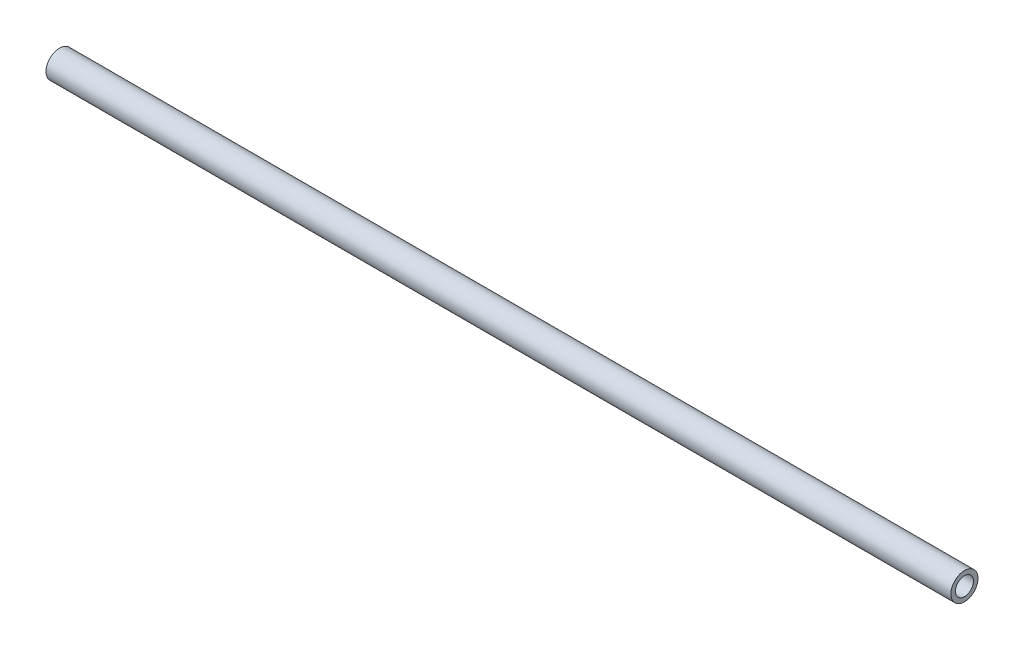
SolidWorks part; units mm, degrees
ref_plane "Front" through (0, 0, 0) normal (0, 0, 1) x (1, 0, 0)
ref_plane "Top" through (0, 0, 0) normal (0, 1, 0) x (1, 0, 0)
ref_plane "Right" through (0, 0, 0) normal (1, 0, 0) x (0, 0, -1)
sketch "Sketch1" plane through (0, 0, 0) normal (1, 0, 0) x (0, 0, -1)
  line L0 (6.35, 0) -> (9.525, 0) construction
  line L1 (6.35, 0) -> (9.525, 0) construction
  line L2 (7.9375, 0) -> (7.9375, 1.0672) construction
  circle A0 centre (0, 0) radius 9.525
  circle A1 centre (0, 0) radius 6.35
  point P4 (9.525, 0)
  point P5 (6.35, 0)
  dimension "OD" = 19.05
  dimension "ID" = 12.7
  dimension "Wall Thickness" = 3.175
sketch "Sketch2" plane through (0, 0, 0) normal (0, 0, 1) x (1, 0, 0)
  line L0 (-317.5, 0) -> (317.5, 0) construction
  point P2 (-293.6875, 0)
  point P3 (293.6875, 0)
  dimension "D1" = 23.8125
  dimension "D2" = 23.8125
sketch "Sketch3" plane through (0, 0, 0) normal (1, 0, 0) x (0, 0, -1)
  circle A0 centre (0, 0) radius 6.35 construction
  circle A1 centre (0, 0) radius 9.525 construction
  circle A2 centre (0, 0) radius 6.35
  circle A3 centre (0, 0) radius 9.525
extrude "Boss-Extrude1" add sketch "Sketch3" along normal mid plane 635
equation "\"D1@Boss-Extrude1\"=\"Length@Sketch2\""
equation "\"D1@Sketch2\"=\"OD@Sketch1\"*1.25"
equation "\"D2@Sketch2\"=\"D1@Sketch2\""
